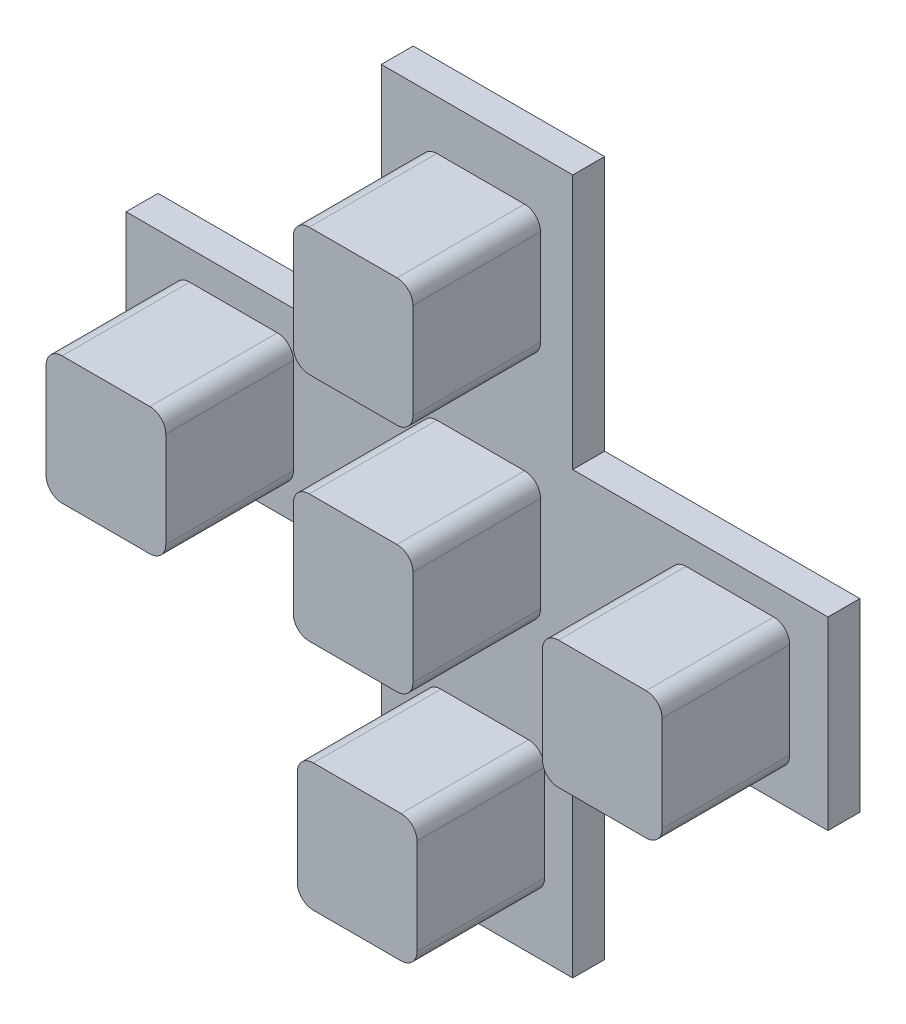
SolidWorks part; units mm, degrees
ref_plane "Front Plane" through (0, 0, 0) normal (0, 0, 1) x (1, 0, 0)
ref_plane "Top Plane" through (0, 0, 0) normal (0, 1, 0) x (1, 0, 0)
ref_plane "Right Plane" through (0, 0, 0) normal (1, 0, 0) x (0, 0, -1)
sketch "Sketch1" plane through (0, 0, 0) normal (0, 0, 1) x (1, 0, 0)
  line L1 (-32.1198, -0.064) -> (-24.6198, -0.064)
  line L2 (-32.1198, -0.064) -> (-32.1198, -8.064)
  line L3 (-32.1198, -8.064) -> (-24.6198, -8.064)
  line L4 (-24.6198, -0.064) -> (-24.6198, -8.064)
  line L5 (-32.1198, -14.542) -> (-24.6198, -14.542)
  line L6 (-32.1198, -14.542) -> (-32.1198, -22.542)
  line L7 (-32.1198, -22.542) -> (-24.6198, -22.542)
  line L8 (-24.6198, -14.542) -> (-24.6198, -22.542)
  line L9 (-16.4988, -14.669) -> (-8.9988, -14.669)
  line L10 (-16.4988, -14.669) -> (-16.4988, -22.669)
  line L11 (-16.4988, -22.669) -> (-8.9988, -22.669)
  line L12 (-8.9988, -14.669) -> (-8.9988, -22.669)
  line L13 (-31.8658, -29.02) -> (-24.3658, -29.02)
  line L14 (-31.8658, -29.02) -> (-31.8658, -37.02)
  line L15 (-31.8658, -37.02) -> (-24.3658, -37.02)
  line L16 (-24.3658, -29.02) -> (-24.3658, -37.02)
  line L17 (-47.6138, -14.796) -> (-40.1138, -14.796)
  line L18 (-47.6138, -14.796) -> (-47.6138, -22.796)
  line L19 (-47.6138, -22.796) -> (-40.1138, -22.796)
  line L20 (-40.1138, -14.796) -> (-40.1138, -22.796)
  point P4 (0, 0)
  point P5 (-24.6198, -4.064)
  point P10 (-12.7488, -14.669)
  point P30 (0, 0)
  point P31 (0, 0)
  point P32 (0, 0)
  point P33 (0, 0)
  point P34 (0, 0)
  point P35 (0, 0)
  point P36 (0, 0)
  point P37 (0, 0)
  point P38 (0, 0)
  dimension "D1" = 6.732
  dimension "D2" = 8
  dimension "D3" = 7.5
  dimension "D4" = 24.6964
  dimension "D5" = 0.064
  dimension "D6" = 6.478
  dimension "D7" = 8
  dimension "D8" = 24.6964
  dimension "D9" = 8.121
  dimension "D10" = 7.5
  dimension "D11" = 6.605
  dimension "D12" = 8
  dimension "D13" = 7.994
  dimension "D14" = 7.5
  dimension "D15" = 7.5
  dimension "D16" = 8
  dimension "D17" = 6.478
  dimension "D18" = 8
  dimension "D19" = 8.248
  dimension "D20" = 7.867
extrude "Boss-Extrude1" add sketch "Sketch1" along normal blind 8
sketch "Sketch3" plane through (0, 0, 0) normal (0, 0, -1) x (-1, 0, 0)
  line L1 (22.6, -12.9683) -> (6.6, -12.9683)
  line L2 (6.6, -12.9683) -> (6.6, -24.5683)
  line L3 (6.6, -24.5683) -> (22.6, -24.5683)
  line L4 (22.6, -24.5683) -> (22.6, -40.5683)
  line L5 (22.6, -40.5683) -> (34.6, -40.5683)
  line L6 (34.6, -40.5683) -> (34.6, -24.5683)
  line L7 (34.6, -24.5683) -> (50.6, -24.5683)
  line L8 (50.6, -24.5683) -> (50.6, -12.9683)
  line L9 (50.6, -12.9683) -> (34.6, -12.9683)
  line L10 (34.6, -12.9683) -> (34.6, 3.0317)
  line L11 (34.6, 3.0317) -> (22.6, 3.0317)
  line L13 (22.6, 3.0317) -> (22.6, -12.9683)
  dimension "D1" = 12
  dimension "D2" = 16
  dimension "D3" = 16
  dimension "D4" = 11.6
  dimension "D5" = 16
  dimension "D6" = 16
  dimension "D7" = 22.6
  dimension "D8" = 3.0317
extrude "Boss-Extrude2" add sketch "Sketch3" along normal blind 2
fillet "Fillet1" radius 1 4 edges at (-31.8658, -29.02, 4) (-24.3658, -29.02, 4) (-24.3658, -37.02, 4) (-31.8658, -37.02, 4)
fillet "Fillet2" radius 1 4 edges at (-32.1198, -14.542, 4) (-24.6198, -14.542, 4) (-24.6198, -22.542, 4) (-32.1198, -22.542, 4)
fillet "Fillet3" radius 1 4 edges at (-40.1138, -22.796, 4) (-47.6138, -22.796, 4) (-47.6138, -14.796, 4) (-40.1138, -14.796, 4)
fillet "Fillet4" radius 1 4 edges at (-24.6198, -8.064, 4) (-32.1198, -8.064, 4) (-32.1198, -0.064, 4) (-24.6198, -0.064, 4)
fillet "Fillet5" radius 1 4 edges at (-8.9988, -14.669, 4) (-8.9988, -22.669, 4) (-16.4988, -22.669, 4) (-16.4988, -14.669, 4)
shell "Shell8" thickness 1 removed face at (-28.6, -18.7683, -2)
